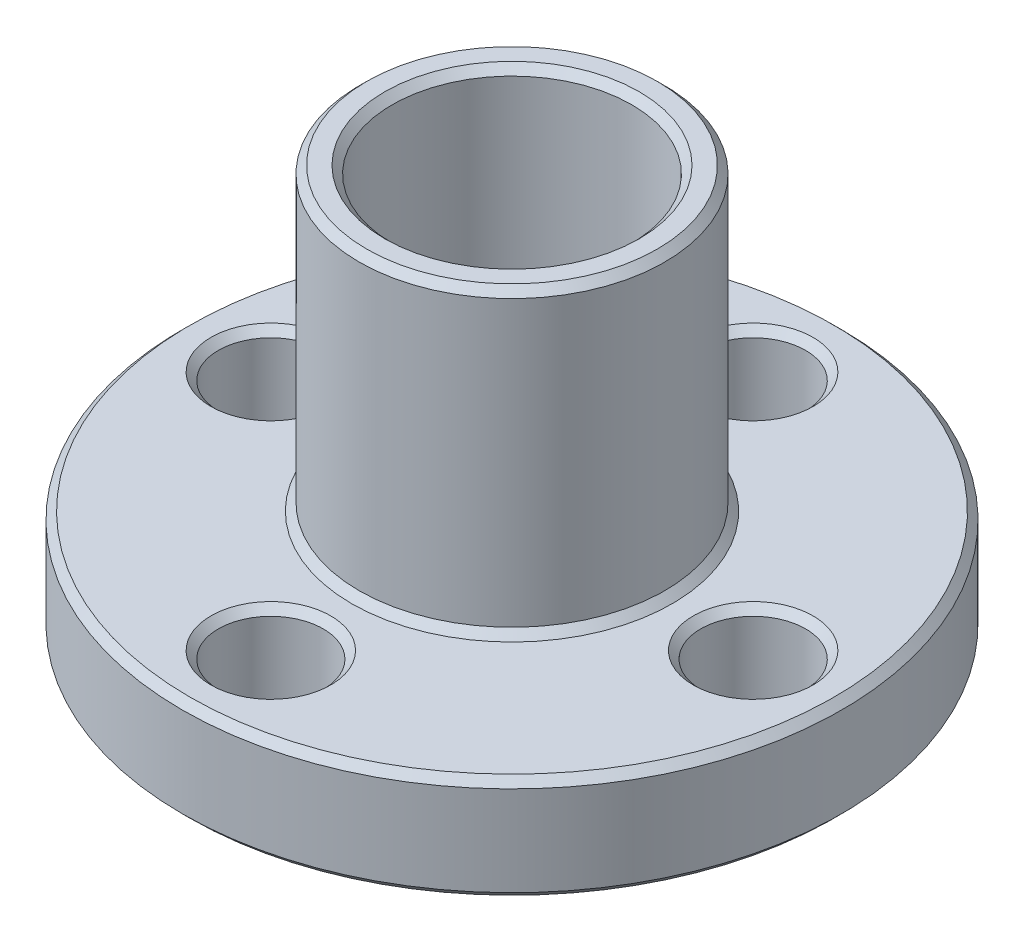
SolidWorks part; units mm, degrees
material "Brass"
ref_plane "Front Plane" through (0, 0, 0) normal (0, 0, 1) x (1, 0, 0)
ref_plane "Top Plane" through (0, 0, 0) normal (0, 1, 0) x (1, 0, 0)
ref_plane "Right Plane" through (0, 0, 0) normal (1, 0, 0) x (0, 0, -1)
sketch "Sketch1" plane through (0, 0, 0) normal (0, 1, 0) x (1, 0, 0)
  circle A0 centre (0, 0) radius 4
  circle A1 centre (0, 0) radius 11
  circle A2 centre (0, 0) radius 5.1
  circle A3 centre (0, 8.05) radius 1.75
  circle A4 centre (8.05, 0) radius 1.75
  circle A5 centre (0, -8.05) radius 1.75
  circle A6 centre (-8.05, 0) radius 1.75
  point P7 (3.6819, -5.7418)
  point P8 (0, 0)
  point P16 (0, 0)
  dimension "D1" = 8
  dimension "D2" = 10.2
  dimension "D3" = 22
  dimension "D5" = 3.5
  dimension "D4" = 8.05
  dimension "D6" = 4
extrude "Boss-Extrude1" add sketch "Sketch1" along normal blind 3.5 contours A1 A2 | A2 A0 region at (-10.6889, 0, 0) region at (-4.9558, 0, 0)
extrude "Boss-Extrude2" add sketch "Sketch1<3>" along normal blind 13.5 contours A2 A0 region at (-4.9558, 0, 0)
sketch "Sketch1<3>" plane through (0, 0, 0) normal (0, 1, 0) x (1, 0, 0) same geometry as "Sketch1"
chamfer "Chamfer1" distance 0.25 angle 45 14 edges at (8.05, 3.5, 1.75) (8.05, 0, 1.75) (0, 3.5, -6.3) (0, 0, -6.3) (0, 0, 9.8) (0, 3.5, 9.8) (-8.05, 0, 1.75) (-8.05, 3.5, 1.75) (0, 13.5, 4) (0, 13.5, 5.1) (0, 3.5, 5.1) (0, 3.5, 11) (0, 0, 11) (0, 0, 4)
equation "\"D4@Sketch1\"=(\"D2@Sketch1\"/2)+((\"D3@Sketch1\"-\"D2@Sketch1\")/4)"
